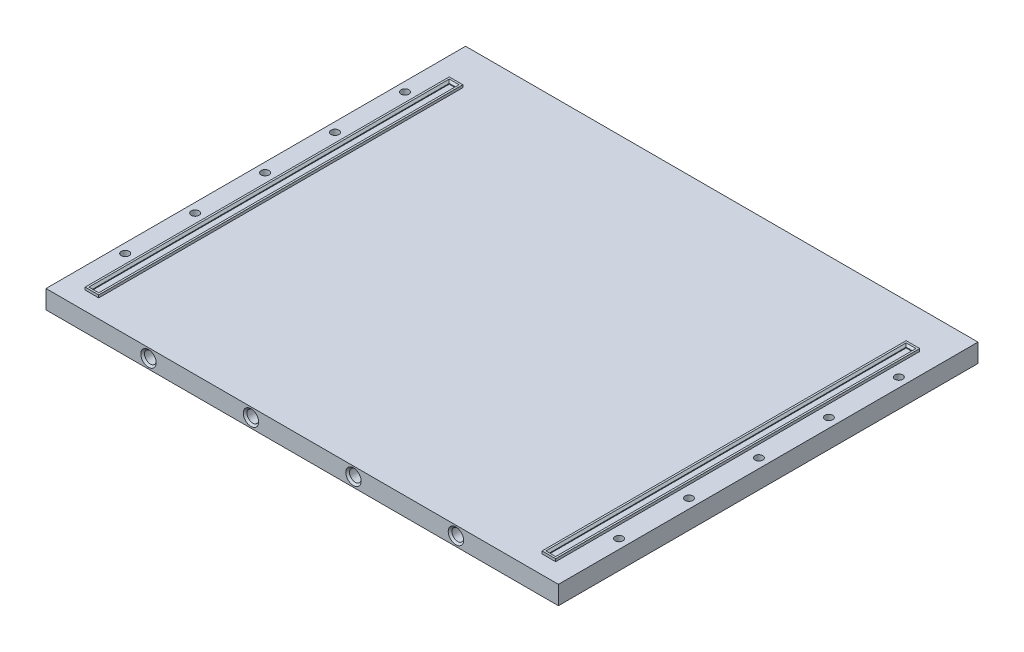
SolidWorks part; units mm, degrees
ref_plane "Спереди" through (0, 0, 0) normal (0, 0, 1) x (1, 0, 0)
ref_plane "Сверху" through (0, 0, 0) normal (0, 1, 0) x (1, 0, 0)
ref_plane "Справа" through (0, 0, 0) normal (1, 0, 0) x (0, 0, -1)
sketch "Эскиз1" plane through (0, 0, 0) normal (0, 1, 0) x (1, 0, 0)
  line L5 (-69, -56.5) -> (69, -56.5)
  line L6 (-69, -56.5) -> (-69, 56.5)
  line L7 (-69, 56.5) -> (69, 56.5)
  line L8 (69, -56.5) -> (69, 56.5)
  line L9 (-69, -56.5) -> (69, 56.5) construction
  line L10 (-69, 56.5) -> (69, -56.5) construction
  point P0 (0, 0)
  dimension "D1" = 113
  dimension "D2" = 138
extrude "Основание" add sketch "Эскиз1" along normal blind 5
sketch "Эскиз6" plane through (0, 0, 0) normal (0, -1, 0) x (1, 0, 0)
  line L0 (0, 45.5668) -> (0, -26.923) construction
  line L1 (-15.8226, 0) -> (3.0664, 0) construction
  line L2 (-37, 37) -> (0, 37) construction
  line L3 (-47, 47) -> (-27, 47)
  line L4 (-47, 47) -> (-47, 27)
  line L5 (-47, 27) -> (-27, 27)
  line L6 (-27, 47) -> (-27, 27)
  line L7 (-47, 47) -> (-27, 27) construction
  line L8 (-47, 27) -> (-27, 47) construction
  line L9 (-37, 37) -> (-37, 0) construction
  line L10 (47, 47) -> (27, 47)
  line L11 (47, 47) -> (47, 27)
  line L12 (47, 27) -> (27, 27)
  line L13 (27, 47) -> (27, 27)
  line L14 (27, -47) -> (27, -27)
  line L15 (47, -27) -> (27, -27)
  line L16 (47, -47) -> (47, -27)
  line L17 (47, -47) -> (27, -47)
  line L18 (-47, -47) -> (-27, -47)
  line L19 (-47, -47) -> (-47, -27)
  line L20 (-47, -27) -> (-27, -27)
  line L21 (-27, -47) -> (-27, -27)
  point P1 (-37, 37)
  dimension "D1" = 20
  dimension "D2" = 37
sketch "Эскиз2" plane through (0, 5, 0) normal (0, 1, 0) x (1, 0, 0)
  line L0 (0, 0) -> (0, -25.5598) construction
  line L1 (-61.525, 37.0772) -> (-61.525, 5.6487) construction
  line L2 (-21.6597, -2.575) -> (12.5108, -2.575) construction
  line L3 (-59.7, 46.45) -> (-63.35, 46.45)
  line L4 (-63.35, 46.45) -> (-63.35, -51.6)
  line L5 (-63.35, -2.575) -> (-62.35, -2.575)
  line L6 (-62.35, -50.6) -> (-62.35, 45.45)
  line L7 (-62.35, 45.45) -> (-60.7, 45.45)
  line L8 (-61.525, 45.45) -> (-61.525, 46.45)
  line L9 (-60.7, -50.6) -> (-60.7, 45.45)
  line L10 (-59.7, -2.575) -> (-60.7, -2.575)
  line L11 (-59.7, 46.45) -> (-59.7, -51.6)
  line L12 (-62.35, -50.6) -> (-60.7, -50.6)
  line L13 (-59.7, -51.6) -> (-63.35, -51.6)
  line L14 (-61.525, -50.6) -> (-61.525, -51.6)
  line L15 (61.525, -50.6) -> (61.525, -51.6)
  line L16 (59.7, -51.6) -> (63.35, -51.6)
  line L17 (62.35, -50.6) -> (60.7, -50.6)
  line L18 (59.7, 46.45) -> (59.7, -51.6)
  line L19 (59.7, -2.575) -> (60.7, -2.575)
  line L20 (60.7, -50.6) -> (60.7, 45.45)
  line L21 (61.525, 45.45) -> (61.525, 46.45)
  line L22 (62.35, 45.45) -> (60.7, 45.45)
  line L23 (62.35, -50.6) -> (62.35, 45.45)
  line L24 (63.35, -2.575) -> (62.35, -2.575)
  line L25 (63.35, 46.45) -> (63.35, -51.6)
  line L26 (59.7, 46.45) -> (63.35, 46.45)
  line L27 (-69, -56.5) -> (69, -56.5) construction
  dimension "D1" = 1
  dimension "D2" = 96.05
  dimension "D3" = 1.65
  dimension "D4" = 121.4
  dimension "D5" = 5.9
extrude "Ложемент материнской платы" add sketch "Эскиз2" along normal blind 0.7 contours L14 L12 L6 L5 L4 L13 | L7 L8 L3 L4 L5 L6 | L11 L3 L8 L7 L9 L10 | L12 L14 L13 L11 L10 L9 | L26 L21 L22 L23 L24 L25 | L26 L18 L19 L20 L22 L21 | L17 L20 L19 L18 L16 L15 | L25 L24 L23 L17 L15 L16 region at (-60.2151, 5, -22.3349) region at (-62.8349, 5, -22.3349) region at (-60.2151, 5, 27.4849) region at (-62.8349, 5, 27.4849) region at (62.8349, 5, 27.4849) region at (60.2151, 5, 27.4849) region at (62.8349, 5, -22.3349) region at (60.2151, 5, -22.3349)
fillet "Фаска первого ложемента" radius 0.5 4 edges at (-61.525, 5.7, -45.45) (-60.7, 5.7, 2.575) (-61.525, 5.7, 50.6) (-62.35, 5.7, 2.575) type face fillet profile chamfer first side face at (-61.525, 5.35, -45.45) first side face at (-61.525, 5.35, 50.6) first side face at (-60.7, 5.35, 2.575) first side face at (-62.35, 5.35, 2.575) second side face at (-61.525, 5.7, 2.575)
fillet "Фаска второго ложемента" radius 0.5 4 edges at (61.525, 5.7, 50.6) (60.7, 5.7, 2.575) (61.525, 5.7, -45.45) (62.35, 5.7, 2.575) type face fillet profile chamfer first side face at (61.525, 5.35, -45.45) first side face at (62.35, 5.35, 2.575) first side face at (60.7, 5.35, 2.575) first side face at (61.525, 5.35, 50.6) second side face at (61.525, 5.7, 2.575)
sketch "Эскиз3" plane through (0, 0, -56.5) normal (0, 0, -1) x (-1, 0, 0)
  line L0 (-69, 0) -> (69, 0) construction
  line L1 (-69, 5) -> (-69, 0) construction
  line L2 (-41.4, 2.5) -> (-69, 2.5) construction
  line L3 (41.4, 2.5) -> (69, 2.5) construction
  line L6 (69, 5) -> (69, 0) construction
  line L7 (-41.4, 2.5) -> (-13.8, 2.5) construction
  line L8 (-13.8, 2.5) -> (13.8, 2.5) construction
  line L9 (13.8, 2.5) -> (41.4, 2.5) construction
  circle A0 centre (-41.4, 2.5) radius 1.575
  circle A1 centre (-13.8, 2.5) radius 1.575
  circle A2 centre (13.8, 2.5) radius 1.575
  circle A3 centre (41.4, 2.5) radius 1.575
  dimension "D4" = 3.15
  dimension "D1" = 2.5
  dimension "D5" = 27.6
  dimension "D3" = 4
extrude "Крепежные отверсия передней и задней стенки" cut sketch "Эскиз3" against normal blind 4.2
ref_plane "Плоскость1" through (0, 0, 0) normal (0, 0, -1) x (-1, 0, 0)
mirror "Зеркальное отражение1" about plane through (0, 0, 0) normal (0, 0, -1) of "Крепежные отверсия передней и задней стенки"
sketch "Эскиз4" plane through (0, 0, 0) normal (0, -1, 0) x (1, 0, 0)
  line L0 (0, 34.8353) -> (0, -23.754) construction
  line L1 (-66.5, 56.5) -> (-66.5, 37.6667) construction
  line L2 (-69, 56.5) -> (69, 56.5) construction
  line L3 (-66.5, 37.6667) -> (-66.5, 18.8333) construction
  line L4 (-66.5, 18.8333) -> (-66.5, 0) construction
  line L5 (-66.5, 0) -> (-66.5, -18.8333) construction
  line L6 (-66.5, -18.8333) -> (-66.5, -37.6667) construction
  line L7 (-66.5, -37.6667) -> (-66.5, -56.5) construction
  line L8 (69, -56.5) -> (-69, -56.5) construction
  line L9 (-69, -56.5) -> (-69, 56.5) construction
  circle A0 centre (-66.5, 37.6667) radius 1.05
  circle A1 centre (-66.5, 18.8333) radius 1.05
  circle A2 centre (-66.5, 0) radius 1.05
  circle A3 centre (-66.5, -18.8333) radius 1.05
  circle A4 centre (-66.5, -37.6667) radius 1.05
  circle A5 centre (66.5, -37.6667) radius 1.05
  circle A6 centre (66.5, -18.8333) radius 1.05
  circle A7 centre (66.5, 0) radius 1.05
  circle A8 centre (66.5, 18.8333) radius 1.05
  circle A9 centre (66.5, 37.6667) radius 1.05
  dimension "D3" = 2.1
  dimension "D2" = 2.5
  dimension "D1" = 5
extrude "Отверстия крепежных винтов" cut sketch "Эскиз4" against normal up to next
sketch "Эскиз5" plane through (0, 0, 0) normal (0, -1, 0) x (1, 0, 0)
  line L0 (0, 88.0608) -> (0, 29.4715) construction
  line L1 (-66.5, 56.5) -> (-66.5, 37.6667) construction
  line L2 (-66.5, 37.6667) -> (-66.5, 18.8333) construction
  line L3 (-66.5, 18.8333) -> (-66.5, 0) construction
  line L4 (-66.5, 0) -> (-66.5, -18.8333) construction
  line L5 (-66.5, -18.8333) -> (-66.5, -37.6667) construction
  line L6 (-66.5, -37.6667) -> (-66.5, -56.5) construction
  line L7 (69, -56.5) -> (-69, -56.5) construction
  line L8 (-69, 56.5) -> (69, 56.5) construction
  circle A0 centre (-66.5, 37.6667) radius 2
  circle A1 centre (-66.5, 18.8333) radius 2
  circle A2 centre (-66.5, 0) radius 2
  circle A3 centre (-66.5, -18.8333) radius 2
  circle A4 centre (-66.5, -37.6667) radius 2
  circle A5 centre (66.5, -37.6667) radius 2
  circle A6 centre (66.5, -18.8333) radius 2
  circle A7 centre (66.5, 0) radius 2
  circle A8 centre (66.5, 18.8333) radius 2
  circle A9 centre (66.5, 37.6667) radius 2
  circle A10 centre (-66.5, -37.6667) radius 1.05 construction
  dimension "D1" = 4
extrude "Потай головок винтов" cut sketch "Эскиз5" against normal blind 3
chamfer "Фаска под запресовку" distance 0.5 angle 45 8 edges at (39.825, 2.5, 56.5) (12.225, 2.5, 56.5) (-15.375, 2.5, 56.5) (-42.975, 2.5, 56.5) (-42.975, 2.5, -56.5) (-15.375, 2.5, -56.5) (12.225, 2.5, -56.5) (39.825, 2.5, -56.5)
